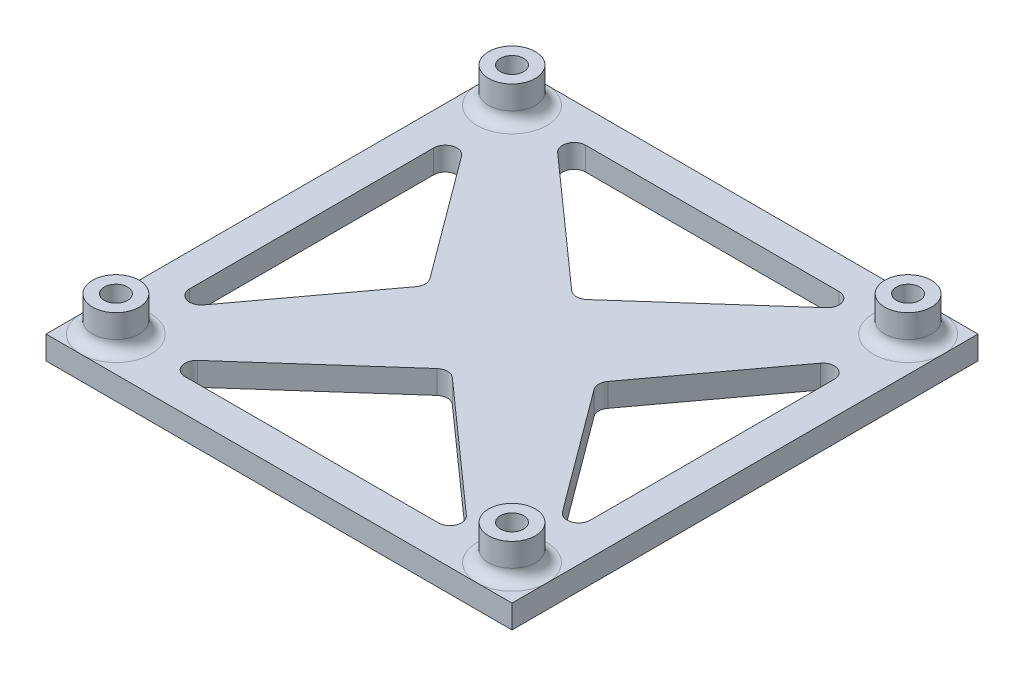
SolidWorks part; units mm, degrees
ref_plane "前基準面" through (0, 0, 0) normal (0, 0, 1) x (1, 0, 0)
ref_plane "上基準面" through (0, 0, 0) normal (0, 1, 0) x (1, 0, 0)
ref_plane "右基準面" through (0, 0, 0) normal (1, 0, 0) x (0, 0, -1)
sketch "草圖1" plane through (0, 0, 0) normal (0, 1, 0) x (1, 0, 0)
  line L0 (-1000, 0) -> (49000, 0) construction
  line L1 (-100, -100) -> (100, -100)
  line L2 (-100, -100) -> (-100, 100)
  line L3 (-100, 100) -> (100, 100)
  line L4 (100, -100) -> (100, 100)
  line L5 (-100, -100) -> (100, 100) construction
  line L6 (-100, 100) -> (100, -100) construction
  line L7 (0, -1000) -> (0, 49000) construction
  circle A0 centre (85, 85) radius 5
  circle A1 centre (-85, 85) radius 5
  circle A2 centre (85, -85) radius 5
  circle A3 centre (-85, -85) radius 5
  point P0 (0, 0)
  dimension "D4" = 10
  dimension "D1" = 200
  dimension "D2" = 200
  dimension "D3" = 15
  dimension "D5" = 15
extrude "填料-伸長1" add sketch "草圖1" along normal blind 7
sketch "草圖2" plane through (0, 7, 0) normal (0, 1, 0) x (1, 0, 0)
  line L0 (-1000, 0) -> (49000, 0) construction
  line L1 (0, -1000) -> (0, 49000) construction
  circle A0 centre (-85, -85) radius 5 construction
  circle A1 centre (85, -85) radius 5 construction
  circle A2 centre (85, 85) radius 5 construction
  circle A3 centre (-85, 85) radius 5 construction
  circle A4 centre (-85, -85) radius 5
  circle A5 centre (85, -85) radius 5
  circle A6 centre (85, 85) radius 5
  circle A7 centre (-85, 85) radius 5
  circle A8 centre (-85, 85) radius 10
  circle A9 centre (85, 85) radius 10
  circle A10 centre (85, -85) radius 10
  circle A11 centre (-85, -85) radius 10
  dimension "D1" = 5
extrude "填料-伸長2" add sketch "草圖2" along normal blind 15
sketch "草圖3" plane through (0, 0, 0) normal (0, -1, 0) x (1, 0, 0)
  line L0 (100, 100) -> (100, -100) construction
  line L1 (100, -100) -> (-100, -100) construction
  line L2 (-100, -100) -> (-100, 100) construction
  line L3 (-100, 100) -> (100, 100) construction
  line L4 (100, 100) -> (100, -100)
  line L5 (100, -100) -> (-100, -100)
  line L6 (-100, -100) -> (-100, 100)
  line L7 (-100, 100) -> (100, 100)
extrude "填料-伸長3" add sketch "草圖3" along normal blind 3
sketch "草圖6" plane through (0, 7, 0) normal (0, 1, 0) x (1, 0, 0)
  line L0 (-1000, 0) -> (49000, 0) construction
  line L1 (0, -1000) -> (0, 49000) construction
  line L2 (-67.5, 85.992) -> (0, 25.992)
  line L3 (0, 25.992) -> (67.5, 85.992)
  line L4 (67.5, 85.992) -> (-67.5, 85.992)
  line L5 (85.992, -67.5) -> (85.992, 67.5)
  line L6 (85.992, 67.5) -> (35.992, 0)
  line L7 (35.992, 0) -> (85.992, -67.5)
  line L8 (-67.5, -85.992) -> (67.5, -85.992)
  line L9 (67.5, -85.992) -> (0, -25.992)
  line L10 (0, -25.992) -> (-67.5, -85.992)
  line L11 (-85.992, 67.5) -> (-85.992, -67.5)
  line L12 (-85.992, -67.5) -> (-35.992, 0)
  line L13 (-35.992, 0) -> (-85.992, 67.5)
  point P20 (0, 0)
  dimension "D1" = 135
  dimension "D2" = 60
  dimension "D3" = 50
  dimension "D4" = 50
extrude "除料-伸長2" cut sketch "草圖6" against normal through all
fillet "圓角2" radius 5 16 edges at (-85.992, 2, 67.5) (-35.992, 2, 0) (-85.992, 2, -67.5) (67.5, 2, 85.992) (-67.5, 2, 85.992) (0, 2, 25.992) (85.992, 2, 67.5) (35.992, 2, 0) (85.992, 2, -67.5) (0, 2, -25.992) (67.5, 2, -85.992) (-67.5, 2, -85.992) (85, 7, 75) (-85, 7, 75) (85, 7, -95) (-85, 7, -95)
